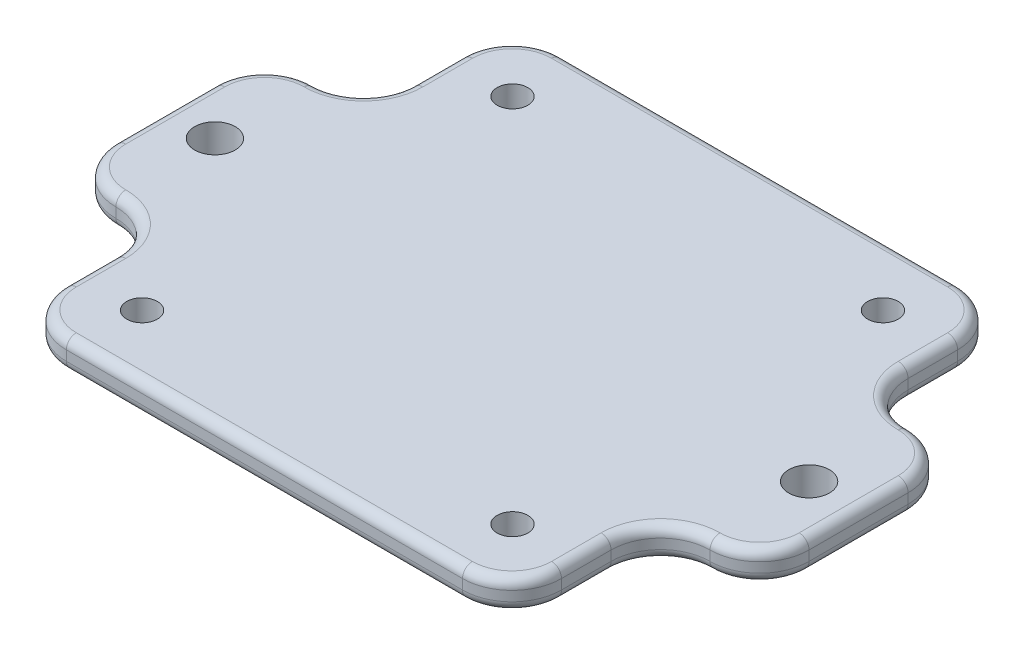
SolidWorks part; units mm, degrees
ref_plane "Alzado" through (0, 0, 0) normal (0, 0, 1) x (1, 0, 0)
ref_plane "Planta" through (0, 0, 0) normal (0, 1, 0) x (1, 0, 0)
ref_plane "Vista lateral" through (0, 0, 0) normal (1, 0, 0) x (0, 0, -1)
sketch "Croquis1" plane through (0, 0, 0) normal (0, 1, 0) x (1, 0, 0)
  line L0 (25, 9.6568) -> (35, 9.6568)
  line L1 (-25, -25.3432) -> (25, -25.3432)
  line L2 (-25, -25.3432) -> (-25, -10.3432)
  line L3 (-25, 24.6568) -> (25, 24.6568)
  line L4 (25, -25.3432) -> (25, -10.3432)
  line L5 (-25, 9.6568) -> (-25, 24.6568)
  line L6 (25, 9.6568) -> (25, 24.6568)
  line L7 (-35, -10.3432) -> (-25, -10.3432)
  line L8 (-35, -10.3432) -> (-35, 9.6568)
  line L9 (-35, 9.6568) -> (-25, 9.6568)
  line L10 (35, -10.3432) -> (35, 9.6568)
  line L17 (25, -10.3432) -> (35, -10.3432)
  circle A0 centre (-18.64, -19.0632) radius 1.55
  circle A1 centre (18.77, -19.0632) radius 1.55
  circle A2 centre (18.77, 18.3468) radius 1.55
  circle A3 centre (-18.64, 18.3468) radius 1.55
  circle A4 centre (-30, -0.3432) radius 2.05
  circle A5 centre (30, -0.3432) radius 2.05
  point P0 (0, 0)
  point P8 (0, 0)
  dimension "D3" = 3.1
  dimension "D4" = 2
  dimension "D6" = 6.28
  dimension "D7" = 6.36
  dimension "D9" = 10
  dimension "D10" = 5
  dimension "D11" = 4.1
  dimension "D12" = 5
  dimension "D13" = 10
  dimension "D14" = 4.1
  dimension "D1" = 50
  dimension "D2" = 50
  dimension "D8" = 70
  dimension "D15" = 20
  dimension "D16" = 15
  dimension "D5" = 2
extrude "Saliente-Extruir1" add sketch "Croquis1" along normal blind 3
fillet "Redondeo1" radius 5 8 edges at (-35, 1.5, -9.6568) (-25, 1.5, -24.6568) (25, 1.5, -24.6568) (35, 1.5, -9.6568) (35, 1.5, 10.3432) (25, 1.5, 25.3432) (-25, 1.5, 25.3432) (-35, 1.5, 10.3432)
fillet "Redondeo2" radius 5 4 edges at (25, 1.5, -9.6568) (-25, 1.5, -9.6568) (-25, 1.5, 10.3432) (25, 1.5, 10.3432)
fillet "Redondeo6" radius 1 20 edges at (-25, 3, 17.8432) (-26.4645, 3, 11.8077) (-33.5355, 3, 8.8787) (-35, 3, 0.3432) (-33.5355, 3, -8.1923) (-26.4645, 3, -11.1213) (-25, 3, -17.1568) (-23.5355, 3, -23.1923) (0, 3, -24.6568) (23.5355, 3, -23.1923) (25, 3, -17.1568) (26.4645, 3, -11.1213) (33.5355, 3, -8.1923) (35, 3, 0.3432) (33.5355, 3, 8.8787) (26.4645, 3, 11.8077) (25, 3, 17.8432) (23.5355, 3, 23.8787) (-23.5355, 3, 23.8787) (0, 3, 25.3432)
fillet "Redondeo7" radius 1 20 edges at (-23.5355, 0, 23.8787) (-25, 0, 17.8432) (-26.4645, 0, 11.8077) (-33.5355, 0, 8.8787) (-35, 0, 0.3432) (-33.5355, 0, -8.1923) (-26.4645, 0, -11.1213) (-25, 0, -17.1568) (-23.5355, 0, -23.1923) (0, 0, -24.6568) (23.5355, 0, -23.1923) (25, 0, -17.1568) (26.4645, 0, -11.1213) (33.5355, 0, -8.1923) (35, 0, 0.3432) (33.5355, 0, 8.8787) (26.4645, 0, 11.8077) (25, 0, 17.8432) (23.5355, 0, 23.8787) (0, 0, 25.3432)
